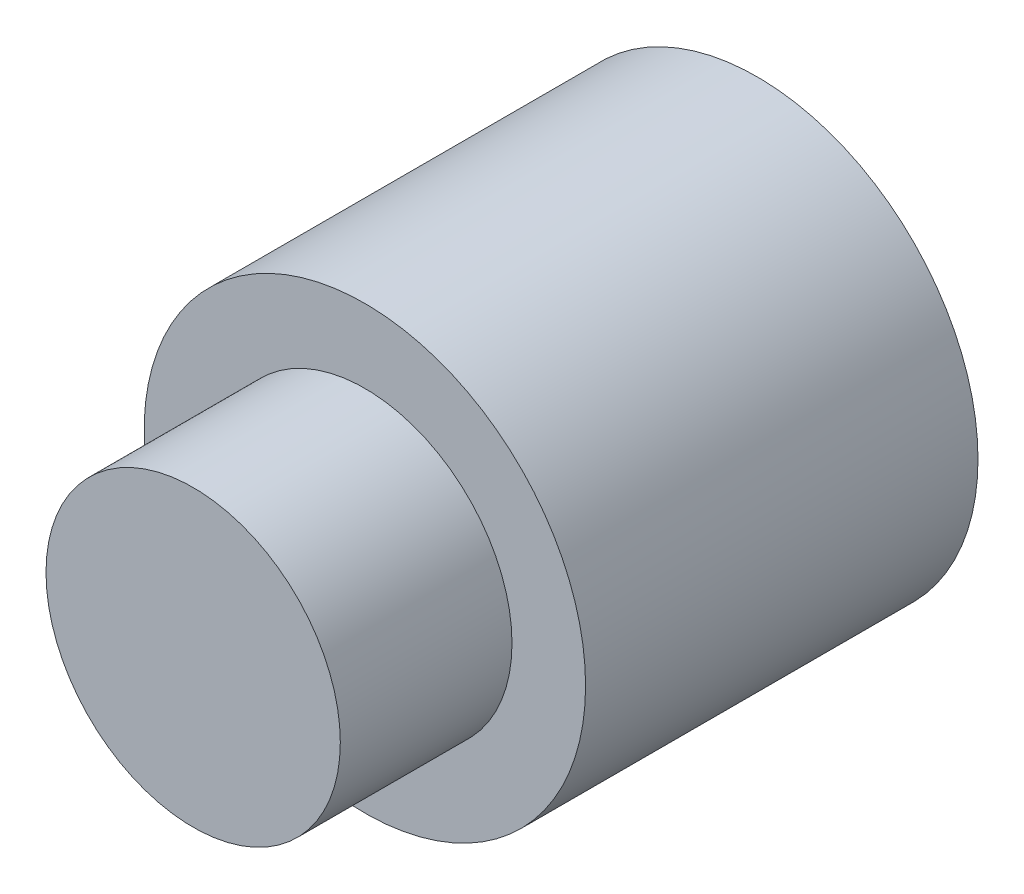
SolidWorks part; units mm, degrees
material "ABS"
ref_plane "Спереди" through (0, 0, 0) normal (0, 0, 1) x (1, 0, 0)
ref_plane "Сверху" through (0, 0, 0) normal (0, 1, 0) x (1, 0, 0)
ref_plane "Справа" through (0, 0, 0) normal (1, 0, 0) x (0, 0, -1)
sketch "Эскиз1" plane through (0, 0, 0) normal (0, 0, 1) x (1, 0, 0)
  circle A0 centre (0, 0) radius 4.5
  dimension "D1" = 9
extrude "Бобышка-Вытянуть1" add sketch "Эскиз1" along normal blind 8 contours A0
sketch "Эскиз2" plane through (0, 0, 8) normal (0, 0, 1) x (1, 0, 0)
  circle A0 centre (0, 0) radius 3
  dimension "D1" = 6
extrude "Бобышка-Вытянуть2" add sketch "Эскиз2" along normal blind 3.5
